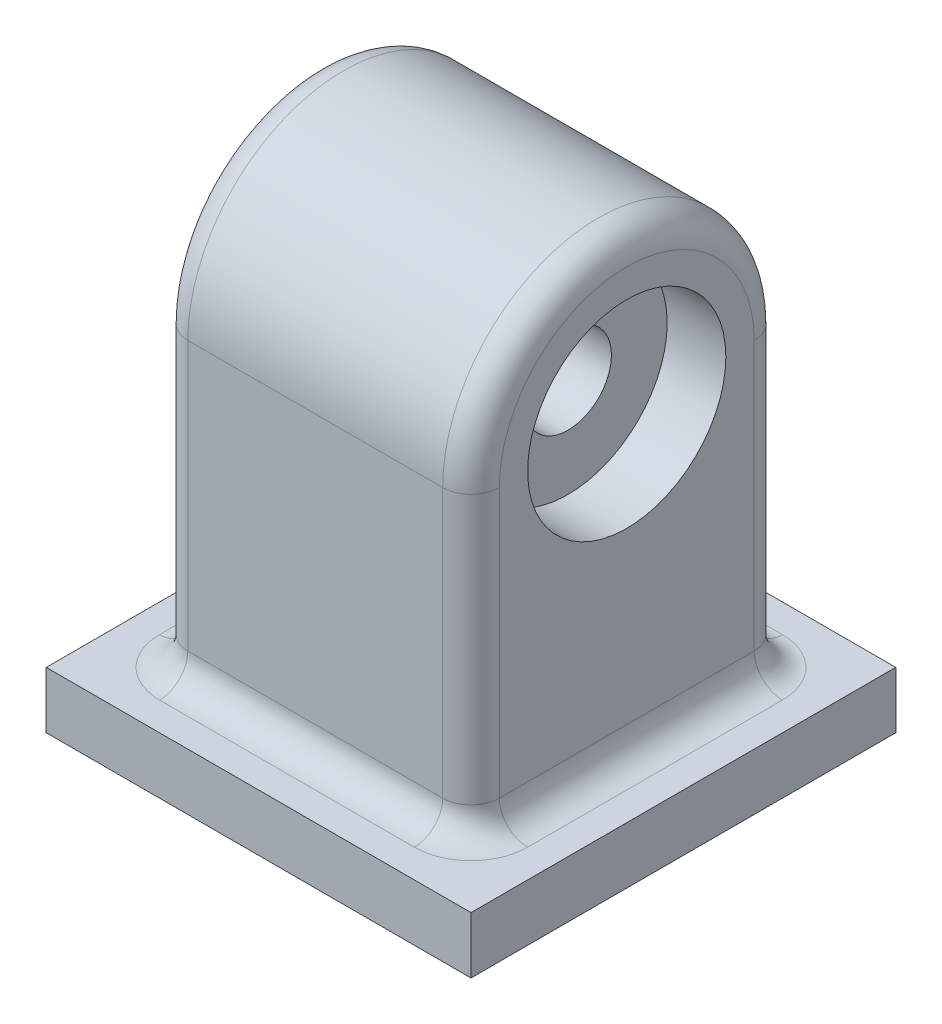
SolidWorks part; units mm, degrees
material "Plain Carbon Steel"
ref_plane "Front Plane" through (0, 0, 0) normal (0, 0, 1) x (1, 0, 0)
ref_plane "Top Plane" through (0, 0, 0) normal (0, 1, 0) x (1, 0, 0)
ref_plane "Right Plane" through (0, 0, 0) normal (1, 0, 0) x (0, 0, -1)
sketch "Sketch1" plane through (0, 0, 0) normal (0, 1, 0) x (1, 0, 0)
  line L1 (95.25, -95.25) -> (-95.25, -95.25)
  line L2 (95.25, -95.25) -> (95.25, 95.25)
  line L3 (95.25, 95.25) -> (-95.25, 95.25)
  line L4 (-95.25, -95.25) -> (-95.25, 95.25)
  line L5 (0, 95.25) -> (0, -95.25) construction
  line L6 (95.25, 0) -> (-95.25, 0) construction
  line L7 (57.15, -57.15) -> (-57.15, -57.15) construction
  line L8 (57.15, -57.15) -> (57.15, 57.15) construction
  line L9 (57.15, 57.15) -> (-57.15, 57.15) construction
  line L10 (-57.15, -57.15) -> (-57.15, 57.15) construction
  line L11 (0, 57.15) -> (0, -57.15) construction
  line L12 (57.15, 0) -> (-57.15, 0) construction
  circle A0 centre (-57.15, 57.15) radius 9.525
  circle A1 centre (57.15, 57.15) radius 9.525
  circle A2 centre (57.15, -57.15) radius 9.525
  circle A3 centre (-57.15, -57.15) radius 9.525
  point P0 (0, 0)
  point P4 (0, 0)
  dimension "D1" = 19.05
  dimension "D2" = 114.3
  dimension "D3" = 114.3
  dimension "D5" = 38.1
extrude "Boss-Extrude1" add sketch "Sketch1" along normal blind 25.4 contours A3 | L4 L1 L2 L3 A3 A2 A1 A0 | A0 | A1 | A2 region at (0, 0, 0) region at (-57.15, 0, -57.15) region at (57.15, 0, -57.15) region at (57.15, 0, 57.15) region at (-57.15, 0, 57.15)
extrude "Boss-Extrude2" add sketch "Sketch1<3>" against normal blind 25.4 contours A3 | A0 | A1 | A2
sketch "Sketch1<3>" plane through (0, 0, 0) normal (0, 1, 0) x (1, 0, 0) same geometry as "Sketch1"
sketch "Sketch3" plane through (0, 25.4, 0) normal (0, 1, 0) x (1, 0, 0)
  line L8 (-69.85, 69.85) -> (-69.85, -69.85)
  line L9 (-69.85, -69.85) -> (69.85, -69.85)
  line L10 (69.85, -69.85) -> (69.85, 69.85)
  line L11 (69.85, 69.85) -> (-69.85, 69.85)
  line L12 (-69.85, 69.85) -> (-69.85, -69.85)
  line L13 (-69.85, -69.85) -> (69.85, -69.85)
  line L14 (69.85, -69.85) -> (69.85, 69.85)
  line L15 (69.85, 69.85) -> (-69.85, 69.85)
  dimension "D1" = 25.4
extrude "Boss-Extrude3" add sketch "Sketch3" along normal blind 203.2
fillet "Fillet1" 2 edges at (0, 228.6, 69.85) (0, 228.6, -69.85) type full round first side face at (0, 127, 69.85) second side face at (0, 127, -69.85) middle face at (0, 228.6, 0)
sketch "Sketch7" plane through (69.85, 0, 0) normal (-1, 0, 0) x (0, 0, 1)
  point P0 (0, 158.75)
hole_wizard "CBORE for 1-1/2 Heavy Hex Bolt1" positions "Sketch7" profile "Sketch6" counterbore size "1-1/2" standard "ANSI Inch" end condition through all
sketch "Sketch6" plane through (69.85, 158.75, 0) normal (0, 1, 0) x (0, 0, -1)
  line L0 (0, 0) -> (0, 165.1)
  line L1 (0, 165.1) -> (19.4462, 165.1)
  line L3 (19.4462, 165.1) -> (19.4462, 26.3144)
  line L4 (19.4462, 26.3144) -> (44.45, 26.3144)
  line L5 (44.45, 26.3144) -> (44.45, 0)
  line L7 (44.45, 0) -> (0, 0)
  line L11 (0, -6.35) -> (0, 107.95) construction
  dimension "Thru Hole Dia." = 38.8925
  dimension "Thru Hole Depth" = 165.1
  dimension "C'Bore Dia." = 88.9
  dimension "C'Bore Depth" = 26.3144
fillet "Fillet2" radius 12.7 10 edges at (0, 25.4, -69.85) (-69.85, 25.4, 0) (69.85, 25.4, 0) (69.85, 92.075, -69.85) (69.85, 228.6, 0) (-69.85, 92.075, -69.85) (-69.85, 228.6, 0) (0, 25.4, 69.85) (69.85, 92.075, 69.85) (-69.85, 92.075, 69.85)
equation "\"D2@Sketch1\"=1.5*3"
equation "\"D3@Sketch1\"=1.5*3"
equation "\"D5@Sketch1\"=\"D4@Sketch1\""
